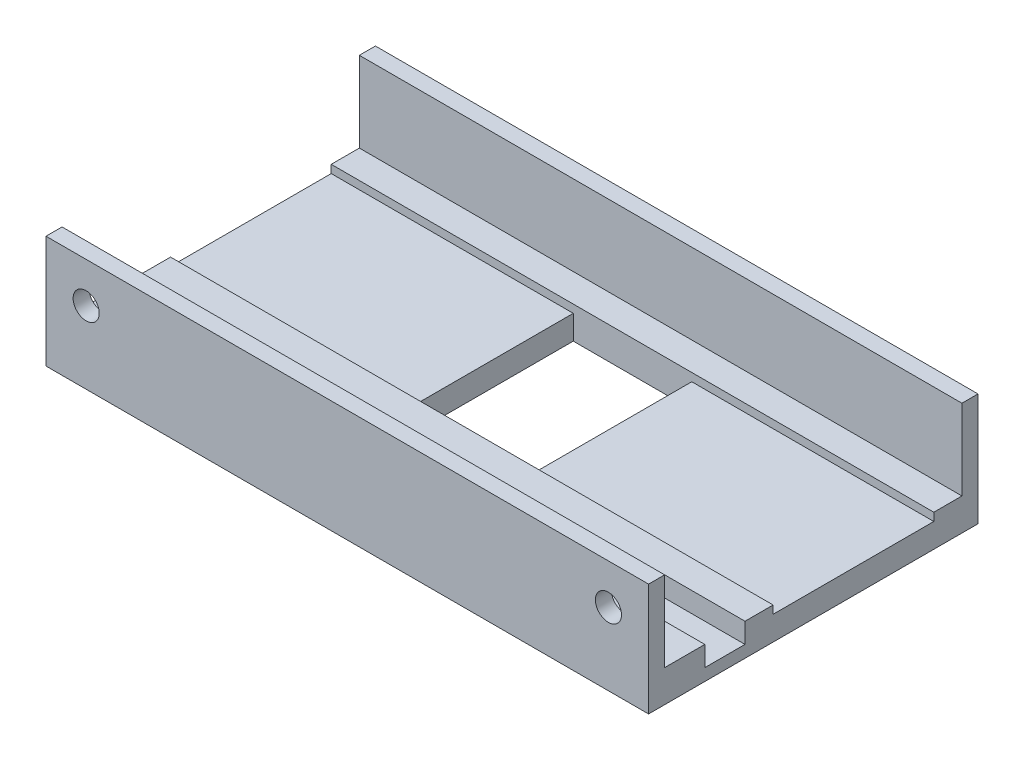
SolidWorks part; units mm, degrees
material "1345 Alloy"
ref_plane "Front Plane" through (0, 0, 0) normal (0, 0, 1) x (1, 0, 0)
ref_plane "Top Plane" through (0, 0, 0) normal (0, 1, 0) x (1, 0, 0)
ref_plane "Right Plane" through (0, 0, 0) normal (1, 0, 0) x (0, 0, -1)
sketch "Sketch1" plane through (0, 0, 0) normal (0, 1, 0) x (1, 0, 0)
  line L1 (-37.5, 20.5) -> (37.5, 20.5)
  line L2 (-37.5, 20.5) -> (-37.5, -20.5)
  line L3 (-37.5, -20.5) -> (37.5, -20.5)
  line L4 (37.5, 20.5) -> (37.5, -20.5)
  line L5 (-37.5, 20.5) -> (37.5, -20.5) construction
  line L6 (-37.5, -20.5) -> (37.5, 20.5) construction
  point P0 (0, 0)
  dimension "D1" = 41
  dimension "D2" = 75
extrude "Boss-Extrude1" add sketch "Sketch1" along normal blind 4
sketch "Sketch2" plane through (0, 4, 0) normal (0, 1, 0) x (1, 0, 0)
  line L0 (37.5, -20.5) -> (37.5, 20.5) construction
  line L1 (-37.5, 20.5) -> (37.5, 20.5)
  line L2 (-37.5, 20.5) -> (-37.5, 18.5)
  line L3 (-37.5, 18.5) -> (37.5, 18.5)
  line L4 (37.5, 20.5) -> (37.5, 18.5)
  dimension "D1" = 2
extrude "Boss-Extrude2" add sketch "Sketch2" along normal blind 10
sketch "Sketch3" plane through (0, 4, 0) normal (0, 1, 0) x (1, 0, 0)
  line L0 (37.5, -20.5) -> (37.5, 18.5) construction
  line L1 (-37.5, -20.5) -> (37.5, -20.5)
  line L2 (-37.5, -20.5) -> (-37.5, -18.5)
  line L3 (-37.5, -18.5) -> (37.5, -18.5)
  line L4 (37.5, -20.5) -> (37.5, -18.5)
  dimension "D1" = 2
extrude "Boss-Extrude3" add sketch "Sketch3" along normal up to surface (10 mm away) up to face at (0, 14, -19.5)
sketch "Sketch6" plane through (0, 4, 0) normal (0, 1, 0) x (1, 0, 0)
  line L0 (-37.5, 18.5) -> (-37.5, -9.5) construction
  line L2 (-37.5, -9.5) -> (37.5039, -9.5) construction
  line L4 (37.5039, -9.5) -> (37.5, 18.5) construction
  line L5 (37.5, 18.5) -> (-37.5, 18.5) construction
  line L7 (-37.5, 5) -> (37.5, 5) construction
  line L8 (0, 18.5) -> (0, -8.5) construction
  line L10 (-7.375, 15) -> (7.375, 15)
  line L11 (-7.375, 15) -> (-7.375, -5)
  line L12 (-7.375, -5) -> (7.375, -5)
  line L13 (7.375, 15) -> (7.375, -5)
  line L14 (-7.375, 15) -> (7.375, -5) construction
  line L15 (-7.375, -5) -> (7.375, 15) construction
  line L16 (-37.5, 18.5) -> (-37.5, -18.5) construction
  line L17 (-22.8126, -9.5) -> (22.1874, -9.5) construction
  point P17 (0, 5)
  dimension "D1" = 14.75
  dimension "D2" = 20
  dimension "D3" = 4.5
extrude "Cut-Extrude3" cut sketch "Sketch6" against normal through all
sketch "Sketch7" plane through (0, 4, 0) normal (0, 1, 0) x (1, 0, 0)
  line L0 (-37.5, 18.5) -> (-37.5, -18.5) construction
  line L1 (-37.5, 15) -> (37.5, 15)
  line L2 (-37.5, 15) -> (-37.5, -5)
  line L3 (-37.5, -5) -> (37.5, -5)
  line L4 (37.5, 15) -> (37.5, -5)
  line L5 (37.5, -18.5) -> (37.5, 18.5) construction
  line L6 (7.375, 15) -> (-7.375, 15) construction
  line L7 (-7.375, -5) -> (7.375, -5) construction
extrude "Cut-Extrude4" cut sketch "Sketch7" against normal blind 1
sketch "Sketch10" plane through (0, 0, 20.5) normal (0, 0, 1) x (1, 0, 0)
  line L0 (0, 0) -> (0, 14) construction
  line L1 (-37.5, 0) -> (37.5, 0) construction
  line L2 (-37.5, 14) -> (37.5, 14) construction
  circle A0 centre (-32.5, 9) radius 1.625
  circle A1 centre (32.5, 9) radius 1.625
  dimension "D1" = 3.25
extrude "Cut-Extrude5" cut sketch "Sketch10" against normal up to surface (2 mm away) up to face at (0, 9, 18.5)
sketch "Sketch11" plane through (0, 4, 0) normal (0, 1, 0) x (1, 0, 0)
  line L0 (0, 0) -> (0, -20.5) construction
  line L1 (-37.5, -8.5) -> (-37.5, -13.5)
  line L2 (-37.5, -20.5) -> (37.5, -20.5) construction
  line L5 (-37.5, -5) -> (-37.5, -18.5) construction
  line L6 (-37.5, -13.5) -> (-27, -13.5)
  line L7 (-27, -13.5) -> (-27, -8.5)
  line L8 (-27, -8.5) -> (-37.5, -8.5)
  line L12 (27, -8.5) -> (37.5, -8.5)
  line L13 (27, -13.5) -> (27, -8.5)
  line L14 (37.5, -13.5) -> (27, -13.5)
  line L15 (37.5, -8.5) -> (37.5, -13.5)
  line L17 (-27.5, -9.5) -> (-27.5, -11.5) construction
  line L18 (37.5, -18.5) -> (-37.5, -18.5) construction
  line L21 (-27.0353, -8.5) -> (-37.5, -8.5) construction
  dimension "D1" = 0.5
  dimension "D2" = 5
extrude "Cut-Extrude6" cut sketch "Sketch11" against normal blind 2.5
